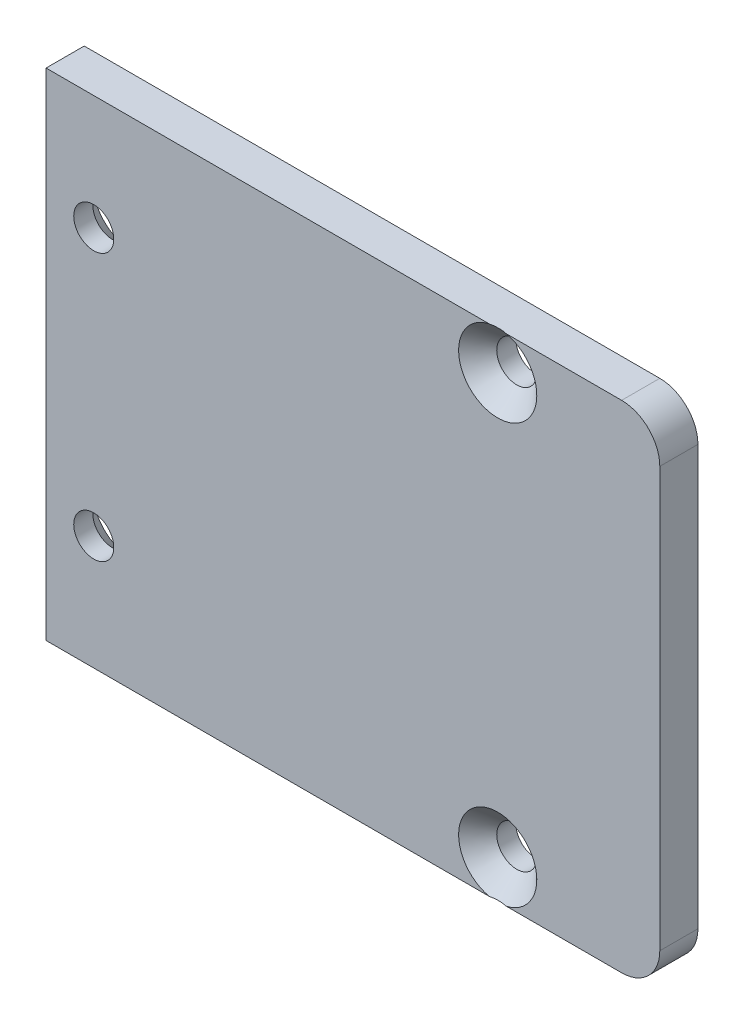
SolidWorks part; units mm, degrees
ref_plane "前视基准面" through (0, 0, 0) normal (0, 0, 1) x (1, 0, 0)
ref_plane "上视基准面" through (0, 0, 0) normal (0, 1, 0) x (1, 0, 0)
ref_plane "右视基准面" through (0, 0, 0) normal (1, 0, 0) x (0, 0, -1)
other "Configuration Table"
sketch "草图2" plane through (0, 0, 0) normal (0, 0, 1) x (1, 0, 0)
  line L0 (-40.9928, -32.4342) -> (-15.4928, -32.4342) construction
  line L1 (15.1907, -6.4342) -> (-16.9928, -6.4342)
  line L2 (15.1907, -6.4342) -> (15.1907, -32.4342)
  line L3 (15.1907, -32.4342) -> (-16.9928, -32.4342)
  line L4 (-16.9928, -6.4342) -> (-16.9928, -32.4342)
  line L5 (-16.9928, 27.5658) -> (-16.9928, -34.4342) construction
  line L6 (13.1907, -6.4342) -> (-12.8093, -6.4342) construction
  point P8 (15.7609, 1.2052)
  point P11 (15.1907, -23.2068)
extrude "凸台-拉伸1" add sketch "草图2" along normal blind 2
fillet "圆角1" radius 2 2 edges at (15.1907, -32.4342, 1) (15.1907, -6.4342, 1)
sketch "草图3" plane through (0, 0, 2) normal (0, 0, 1) x (1, 0, 0)
  circle A0 centre (6.6907, -8.4342) radius 1.05
  circle A1 centre (6.6907, -30.4342) radius 1.05
  dimension "D1" = 2.1
extrude "切除-拉伸1" cut sketch "草图3" against normal up to next
sketch "草图4" plane through (0, 0, 0) normal (0, 0, -1) x (-1, 0, 0)
  line L0 (-13.1907, -6.4342) -> (16.9928, -6.4342) construction
  line L2 (16.9928, -34.4342) -> (16.9928, 27.5658) construction
  line L4 (16.9928, -32.4342) -> (-13.1907, -32.4342) construction
  circle A0 centre (14.4928, -12.4342) radius 1.05
  circle A1 centre (14.4928, -26.4342) radius 1.05
  point P10 (0, 0)
  dimension "D1" = 2.1
  dimension "D2" = 6
  dimension "D3" = 6
  dimension "D4" = 2.5
extrude "切除-拉伸2" cut sketch "草图4" against normal up to next
chamfer "倒角1" distance 1 angle 45 2 edges at (-15.5428, -12.4342, 0) (-15.5428, -26.4342, 0)
chamfer "倒角2" distance 1 angle 45 2 edges at (7.7407, -30.4342, 2) (7.7407, -8.4342, 2)
